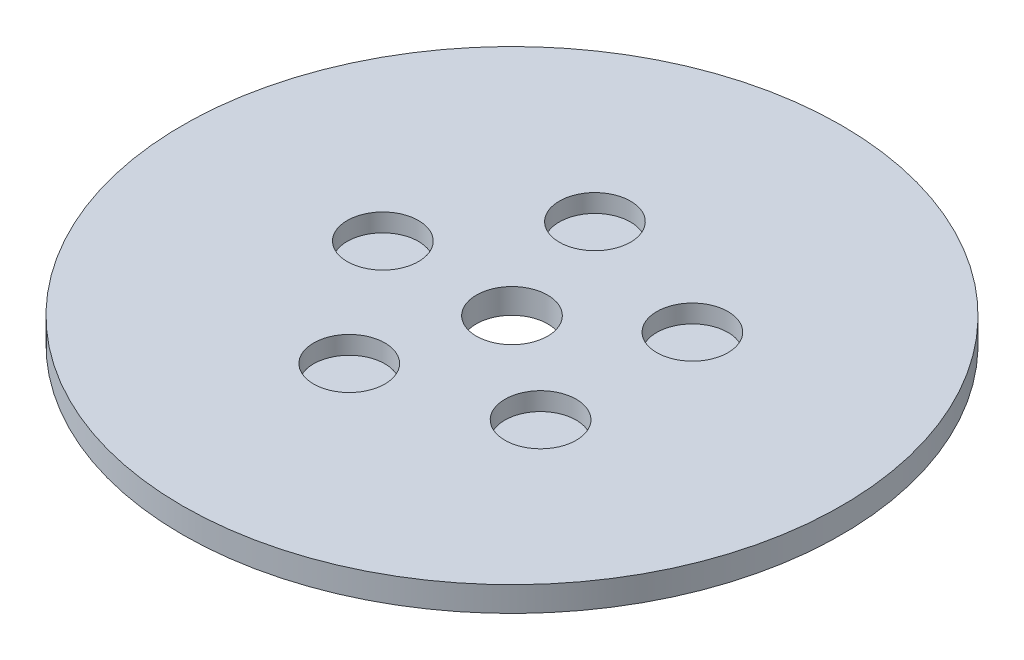
SolidWorks part; units mm, degrees
ref_plane "Front Plane" through (0, 0, 0) normal (0, 0, 1) x (1, 0, 0)
ref_plane "Top Plane" through (0, 0, 0) normal (0, 1, 0) x (1, 0, 0)
ref_plane "Right Plane" through (0, 0, 0) normal (1, 0, 0) x (0, 0, -1)
sketch "Sketch1" plane through (0, 0, 0) normal (0, 1, 0) x (1, 0, 0)
  circle A0 centre (0, 0) radius 92.5
  dimension "FLANGE_OD" = 185
extrude "Boss-Extrude1" add sketch "Sketch1" along normal blind 7
sketch "Sketch2" plane through (0, 0, 0) normal (0, 1, 0) x (1, 0, 0)
  circle A0 centre (0, 0) radius 10
  dimension "BORE_D" = 20
extrude "Cut-Extrude1" cut sketch "Sketch2" along normal through all
sketch "Sketch3" plane through (0, 7, 0) normal (0, 1, 0) x (1, 0, 0)
  circle A0 centre (0, 0) radius 36.2496 construction
  circle A1 centre (-36.2496, 0) radius 10
  dimension "BOLT_D" = 20
  dimension "BOLT_PCD" = 72.4993
extrude "Cut-Extrude2" cut sketch "Sketch3" against normal blind 5.0794
pattern_circular "CirPattern1" count 5 over 360 about axis through (0, 0, 0) along (0, 1, 0) of "Cut-Extrude2"
